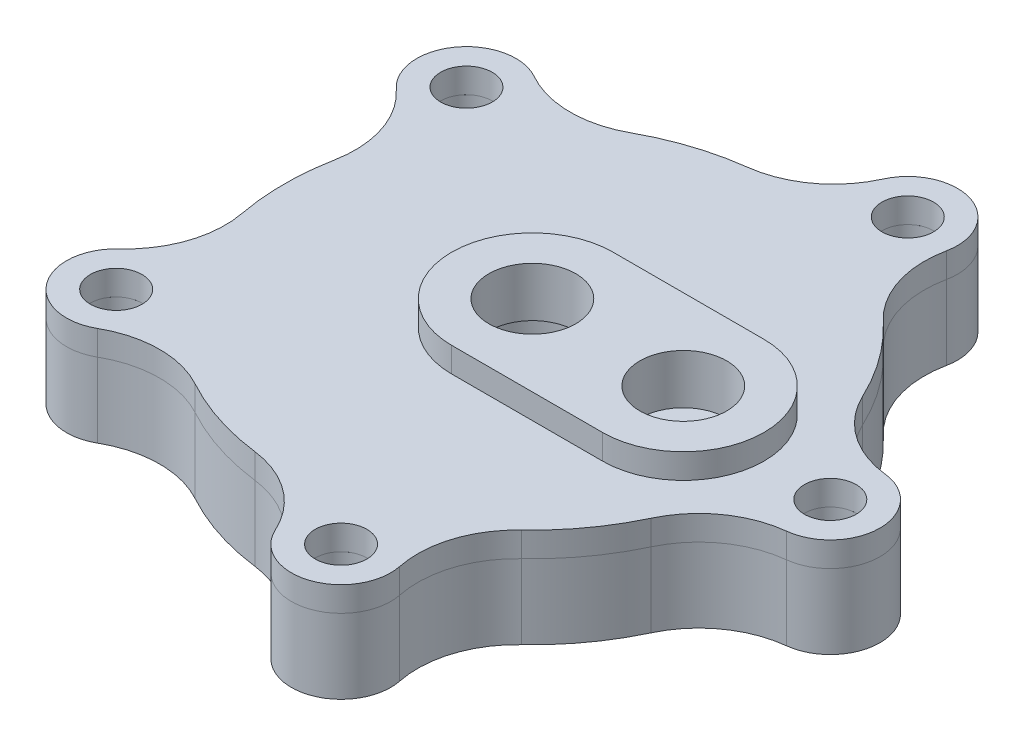
SolidWorks part; units mm, degrees
note: The reader was unsure of these and kept them because the rebuilt part matched: shared geometry of "Sketch1<3>", "Sketch2<4>", "Sketch1<6>", "Sketch1<7>", "Sketch3<3>".
ref_plane "Front Plane" through (0, 0, 0) normal (0, 0, 1) x (1, 0, 0)
ref_plane "Top Plane" through (0, 0, 0) normal (0, 1, 0) x (1, 0, 0)
ref_plane "Right Plane" through (0, 0, 0) normal (1, 0, 0) x (0, 0, -1)
sketch "Sketch1" plane through (0, 0, 0) normal (0, 0, 1) x (1, 0, 0)
  line L6 (31.75, 3.175) -> (0, 3.175)
  line L7 (0, 3.175) -> (0, 0)
  line L8 (6.35, 3.175) -> (6.35, 6.35)
  line L9 (6.35, 6.35) -> (11.1125, 6.35)
  line L10 (11.1125, 6.35) -> (11.1125, 3.175)
  line L11 (8.0541, 6.35) -> (8.0541, 5.2123)
  line L12 (8.0541, 5.2123) -> (9.6416, 5.2123)
  line L13 (9.6416, 5.2123) -> (9.6416, 6.35)
  line L14 (31.75, 3.175) -> (31.75, 6.35)
  line L15 (31.75, 6.35) -> (26.9875, 6.35)
  line L16 (26.9875, 6.35) -> (26.9875, 3.175)
  line L17 (28.5755, 6.35) -> (28.5755, 5.2123)
  line L18 (28.5755, 5.2123) -> (30.163, 5.2123)
  line L19 (30.163, 5.2123) -> (30.163, 6.35)
  line L20 (31.75, 3.175) -> (31.75, 0)
  line L21 (31.75, 0) -> (0, 0)
  line L22 (31.75, 6.35) -> (31.75, 9.525)
  line L23 (31.75, 9.525) -> (5.5562, 9.525)
  line L24 (5.5562, 9.525) -> (5.5563, 6.35)
  line L25 (5.5563, 6.35) -> (6.35, 6.35)
  line L26 (11.1125, 6.35) -> (26.9875, 6.35)
  line L27 (31.75, 0) -> (31.75, -3.175)
  line L28 (31.75, -3.175) -> (24.13, -3.175)
  line L29 (24.13, -3.175) -> (24.13, 0)
  line L30 (3.175, 3.175) -> (5.0081, 0)
  line L31 (5.0081, 0) -> (7.2425, -3.87)
  line L32 (14.2875, 3.175) -> (11.1125, 0)
  line L33 (11.1125, 0) -> (7.2425, -3.87)
  line L34 (13.5691, 3.175) -> (10.3941, 0)
  line L35 (15.0059, 3.175) -> (11.8309, 0)
  line L36 (2.5884, 3.175) -> (4.4215, 0)
  line L37 (3.7616, 3.175) -> (5.5947, 0)
  line L38 (13.4815, 2.369) -> (13.1223, 2.7282) construction
  line L39 (13.4815, 2.369) -> (13.8407, 2.0098) construction
  line L40 (4.2846, 2.2691) -> (3.8447, 2.0151) construction
  line L41 (3.8447, 2.0151) -> (3.4047, 1.7611) construction
  line L42 (11.8309, 0) -> (11.1125, -0.7184)
  line L43 (11.1125, -0.7184) -> (10.3941, 0)
  line L44 (4.4215, 0) -> (4.7148, -0.508)
  line L45 (4.7148, -0.508) -> (5.5947, 0)
  point P44 (28.5755, 5.2123)
  dimension "D1" = 4.7625
  dimension "D2" = 1.5875
  dimension "D3" = 4.7625
  dimension "D4" = 3.175
  dimension "D5" = 6.35
  dimension "D6" = 3.175
  dimension "D7" = 24.13
  dimension "D8" = 31.75
  dimension "D9" = 3.175
  dimension "D10" = 60
  dimension "D11" = 5.5562
  dimension "D12" = 3.175
  dimension "D13" = 3.175
  dimension "D14" = 45
  dimension "D15" = 3.175
  dimension "D16" = 1.016
  dimension "D17" = 1.016
revolve "Revolve1" add sketch "Sketch1" angle 360 about L7
revolve "Revolve2" add sketch "Sketch1<3>" angle 360 about L7
sketch "Sketch1<3>" plane through (0, 0, 0) normal (0, 0, 1) x (1, 0, 0) same geometry as "Sketch1"
sketch "Sketch2" plane through (0, 9.525, 0) normal (0, 1, 0) x (1, 0, 0)
  line L0 (38.1, 0) -> (0, 0) construction
  line L1 (0, 0) -> (42.0604, 0) construction
  line L2 (38.1, 6.35) -> (31.1085, 6.35)
  line L3 (38.1, -6.35) -> (31.1085, -6.35)
  line L4 (5.7343, -38.1975) -> (3.5739, -31.5482)
  line L5 (17.8128, -34.273) -> (15.6523, -27.6237)
  line L6 (-34.556, -17.2574) -> (-28.8998, -13.1479)
  line L7 (-27.0911, -27.5319) -> (-21.4349, -23.4224)
  line L8 (-27.0911, 27.5319) -> (-21.4349, 23.4224)
  line L9 (-34.556, 17.2574) -> (-28.8998, 13.1479)
  line L10 (17.8128, 34.273) -> (15.6523, 27.6237)
  line L11 (5.7343, 38.1975) -> (3.5739, 31.5482)
  circle A0 centre (38.1, 0) radius 3.302
  circle A1 centre (38.1, 0) radius 6.35
  circle A2 centre (11.7735, -36.2353) radius 3.302
  circle A3 centre (0, 0) radius 31.75
  circle A4 centre (0, 0) radius 31.75
  circle A5 centre (11.7735, -36.2353) radius 6.35
  circle A6 centre (-30.8235, -22.3946) radius 3.302
  circle A7 centre (-30.8235, -22.3946) radius 6.35
  circle A8 centre (-30.8235, 22.3946) radius 3.302
  circle A9 centre (-30.8235, 22.3946) radius 6.35
  circle A10 centre (11.7735, 36.2353) radius 3.302
  circle A11 centre (11.7735, 36.2353) radius 6.35
  circle A12 centre (0, 0) radius 31.75 construction
  point P24 (0, 0)
  point P28 (15.8104, 27.5335)
  point P47 (0, 0)
  point P48 (0, 0)
  point P49 (38.1, 0)
  circle M3 centre (0, 0) radius 31.75
  dimension "D2" = 12.7
  dimension "D3" = 6.604
  dimension "D1" = 38.1
  dimension "D6" = 5
  dimension "D4" = 0
  dimension "D5" = 5
extrude "Boss-Extrude1" add sketch "Sketch2" against normal blind 3.175
extrude "Boss-Extrude2" add sketch "Sketch2<4>" against normal up to surface (9.525 mm away) from surface at -12.7 contours A1 L2 M3 | A1 A0 | A1 L3 M3 | A5 L5 A4 | A5 A2 | A5 L4 M3 | A7 L7 A4 | A7 A6 | A7 L6 M3 | A9 L9 A4 | A9 A8 | A9 L8 M3 | A11 L10 M3 | A11 A10 | A11 L11 A4
sketch "Sketch2<4>" plane through (0, 9.525, 0) normal (0, 1, 0) x (1, 0, 0) same geometry as "Sketch2"
fillet "Fillet1" radius 12.7 10 edges at (-21.4349, 7.9375, 23.4224) (3.5739, 7.9375, 31.5482) (15.6523, 7.9375, 27.6237) (31.1085, 7.9375, 6.35) (31.1085, 7.9375, -6.35) (15.6523, 7.9375, -27.6237) (3.5739, 7.9375, -31.5482) (-21.4349, 7.9375, -23.4224) (-28.8998, 7.9375, 13.1479) (-28.8998, 7.9375, -13.1479)
revolve "Cut-Revolve1" cut sketch "Sketch1<6>" angle 360 about L32
sketch "Sketch1<6>" plane through (0, 0, 0) normal (0, 0, 1) x (1, 0, 0) same geometry as "Sketch1"
revolve "Cut-Revolve2" cut sketch "Sketch1<7>" angle 360 about L30
sketch "Sketch1<7>" plane through (0, 0, 0) normal (0, 0, 1) x (1, 0, 0) same geometry as "Sketch1"
ref_axis "Axis1" through (0, -3.175, 0) along (0, 1, 0)
pattern_circular "CirPattern1" count 3 over 360 about axis through (0, -3.175, 0) along (0, 1, 0) of "Cut-Revolve2", "Cut-Revolve1"
sketch "Sketch3" plane through (0, 9.525, 0) normal (0, 1, 0) x (1, 0, 0)
  line L0 (19.304, 10.3187) -> (0, 10.3187)
  line L1 (19.304, -10.3187) -> (0, -10.3187)
  circle A0 centre (19.304, 0) radius 5.5563
  arc A2 (0, 10.3187) -> (0, -10.3187) centre (0, 0) ccw
  circle A3 centre (0, 0) radius 5.5563 construction
  circle A4 centre (0, 0) radius 5.5563
  arc A7 (19.304, -10.3187) -> (19.304, 10.3187) centre (19.304, 0) ccw
  point P13 (-19.6326, -9.5625)
  point P14 (22.6696, 0)
  dimension "D1" = 20.6375
  dimension "D2" = 19.304
extrude "Boss-Extrude3" add sketch "Sketch3" along normal blind 3.175
extrude "Cut-Extrude1" cut sketch "Sketch3<3>" against normal blind 3.175 contours A0
sketch "Sketch3<3>" plane through (0, 9.525, 0) normal (0, 1, 0) x (1, 0, 0) same geometry as "Sketch3"
fillet "Fillet3" radius 12.7 40 edges at (5.7343, 1.5875, -38.1975) (17.8128, 1.5875, -34.273) (16.7325, 6.35, -30.9483) (15.6523, 1.5875, -27.6237) (16.7325, -3.175, -30.9483) (3.5739, 1.5875, -31.5482) (4.6541, -3.175, -34.8729) (4.6541, 6.35, -34.8729) (38.1, 1.5875, -6.35) (38.1, 1.5875, 6.35) (34.6043, 6.35, 6.35) (31.1085, 1.5875, 6.35) (34.6043, -3.175, 6.35) (31.1085, 1.5875, -6.35) (34.6043, -3.175, -6.35) (34.6043, 6.35, -6.35) (17.8128, 1.5875, 34.273) (5.7343, 1.5875, 38.1975) (4.6541, 6.35, 34.8729) (3.5739, 1.5875, 31.5482) (4.6541, -3.175, 34.8729) (15.6523, 1.5875, 27.6237) (16.7325, -3.175, 30.9483) (16.7325, 6.35, 30.9483) (-27.0911, 1.5875, 27.5319) (-34.556, 1.5875, 17.2574) (-31.7279, 6.35, 15.2026) (-28.8998, 1.5875, 13.1479) (-31.7279, -3.175, 15.2026) (-21.4349, 1.5875, 23.4224) (-24.263, -3.175, 25.4771) (-24.263, 6.35, 25.4771) (-34.556, 1.5875, -17.2574) (-27.0911, 1.5875, -27.5319) (-24.263, 6.35, -25.4771) (-21.4349, 1.5875, -23.4224) (-24.263, -3.175, -25.4771) (-28.8998, 1.5875, -13.1479) (-31.7279, -3.175, -15.2026) (-31.7279, 6.35, -15.2026)
sketch "Sketch4" plane through (0, 0, 0) normal (0, -1, 0) x (-1, 0, 0)
  circle A0 centre (0, 0) radius 19.6723
  circle A1 centre (0, 0) radius 22.2885
  dimension "D1" = 39.3446
  dimension "D2" = 44.577
extrude "Cut-Extrude3" cut sketch "Sketch4" against normal blind 2.286
